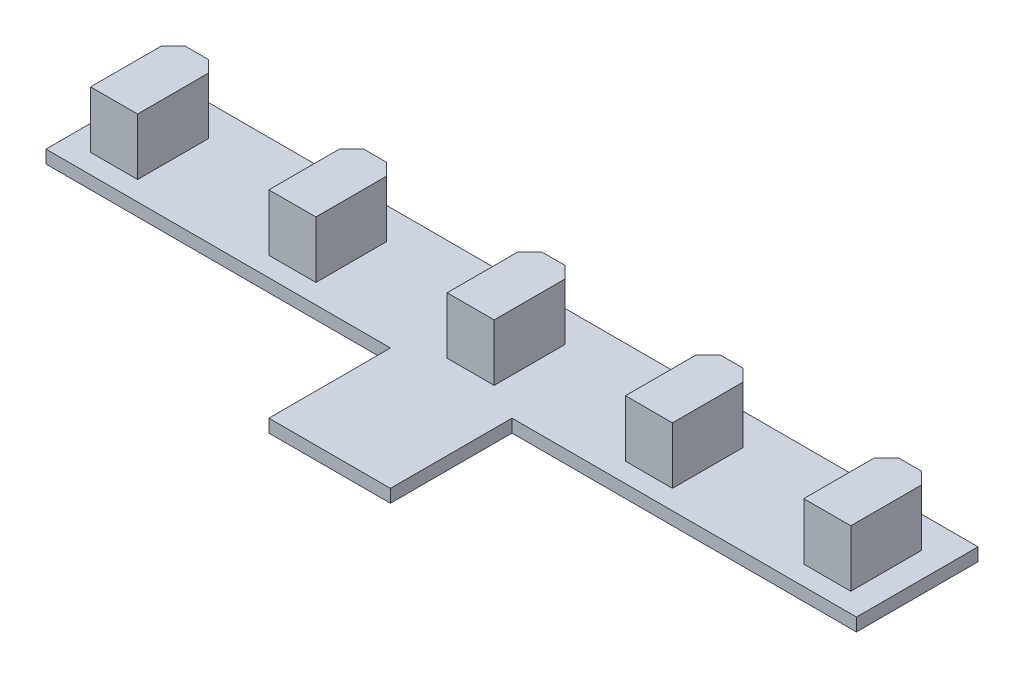
SolidWorks part; units mm, degrees
ref_plane "Front Plane" through (0, 0, 0) normal (0, 0, 1) x (1, 0, 0)
ref_plane "Top Plane" through (0, 0, 0) normal (0, 1, 0) x (1, 0, 0)
ref_plane "Right Plane" through (0, 0, 0) normal (1, 0, 0) x (0, 0, -1)
sketch "Sketch1" plane through (0, 0, 0) normal (0, 1, 0) x (1, 0, 0)
  line L0 (0, -55) -> (0, 55) construction
  line L1 (-7.5, -4.5) -> (7.5, -4.5)
  line L2 (-7.5, -4.5) -> (-7.5, 10.5)
  line L3 (-7.5, 10.5) -> (7.5, 10.5)
  line L4 (7.5, -4.5) -> (7.5, 10.5)
  line L5 (-7.5, -4.5) -> (7.5, 10.5) construction
  line L6 (-7.5, 10.5) -> (7.5, -4.5) construction
  line L7 (-5.28, -2.5) -> (5.28, -2.5)
  line L8 (-5.28, -2.5) -> (-5.28, 2.5)
  line L9 (-5.28, 2.5) -> (5.28, 2.5)
  line L10 (5.28, -2.5) -> (5.28, 2.5)
  line L11 (-5.28, -2.5) -> (5.28, 2.5) construction
  line L12 (-5.28, 2.5) -> (5.28, -2.5) construction
  line L13 (-2.9, 12.9) -> (2.9, 12.9)
  line L14 (-50, 25.5) -> (50, 25.5)
  line L15 (-50, 25.5) -> (-50, 10.5)
  line L16 (-50, 10.5) -> (50, 10.5)
  line L17 (50, 25.5) -> (50, 10.5)
  line L18 (-50, 25.5) -> (50, 10.5) construction
  line L19 (-50, 10.5) -> (50, 25.5) construction
  line L24 (-1.4307, 23.1) -> (1.4307, 23.1)
  line L25 (0, 12.9) -> (0, 23.1) construction
  line L26 (-2.9, 12.9) -> (-2.9, 21.6307)
  line L27 (-2.9, 21.6307) -> (-1.4307, 23.1)
  line L28 (1.4307, 23.1) -> (2.9, 21.6307)
  line L29 (2.9, 21.6307) -> (2.9, 12.9)
  line L30 (24.9, 21.6307) -> (24.9, 12.9)
  line L31 (19.1, 12.9) -> (24.9, 12.9)
  line L32 (19.1, 12.9) -> (19.1, 21.6307)
  line L33 (19.1, 21.6307) -> (20.5693, 23.1)
  line L34 (20.5693, 23.1) -> (23.4307, 23.1)
  line L35 (23.4307, 23.1) -> (24.9, 21.6307)
  line L36 (46.9, 21.6307) -> (46.9, 12.9)
  line L37 (41.1, 12.9) -> (46.9, 12.9)
  line L38 (41.1, 12.9) -> (41.1, 21.6307)
  line L39 (41.1, 21.6307) -> (42.5693, 23.1)
  line L40 (42.5693, 23.1) -> (45.4307, 23.1)
  line L41 (45.4307, 23.1) -> (46.9, 21.6307)
  line L42 (-19.1, 21.6307) -> (-19.1, 12.9)
  line L43 (-24.9, 12.9) -> (-19.1, 12.9)
  line L44 (-24.9, 12.9) -> (-24.9, 21.6307)
  line L45 (-24.9, 21.6307) -> (-23.4307, 23.1)
  line L46 (-23.4307, 23.1) -> (-20.5693, 23.1)
  line L47 (-20.5693, 23.1) -> (-19.1, 21.6307)
  line L48 (-41.1, 21.6307) -> (-41.1, 12.9)
  line L49 (-46.9, 12.9) -> (-41.1, 12.9)
  line L50 (-46.9, 12.9) -> (-46.9, 21.6307)
  line L51 (-46.9, 21.6307) -> (-45.4307, 23.1)
  line L52 (-45.4307, 23.1) -> (-42.5693, 23.1)
  line L53 (-42.5693, 23.1) -> (-41.1, 21.6307)
  point P0 (0, 3)
  point P5 (0, 0)
  point P13 (0, 18)
  point P15 (0, 18)
  point P26 (0, 18)
  dimension "D1" = 15
  dimension "D2" = 15
  dimension "D3" = 10.56
  dimension "D4" = 5
  dimension "D5" = 2
  dimension "D6" = 15
  dimension "D7" = 100
  dimension "D8" = 45
  dimension "D9" = 10.2
  dimension "D10" = 5.8
  dimension "D11" = 3
  dimension "D12" = 3
extrude "Boss-Extrude1" add sketch "Sketch1" along normal blind 1.6 contours L1 L4 L3 L2 L10 L7 L8 L9 | L7 L10 L9 L8 | L17 L14 L15 L16 L3 L28 L29 L13 L26 L27 L24 L34 L35 L30 L31 L32 L33 L40 L41 L36 L37 L38 L39 L46 L47 L42 L43 L44 L45 L52 L53 L48 L49 L50 L51 region at (0, 0, -3.9199) region at (-28.75, 0, -11.5112) region at (0, 0, 0)
extrude "Boss-Extrude2" add sketch "Sketch1<3>" against normal blind 2 contours L7 L10 L9 L8 region at (0, 0, 0)
sketch "Sketch1<3>" plane through (0, 0, 0) normal (0, 1, 0) x (1, 0, 0) same geometry as "Sketch1"
extrude "Boss-Extrude3" add sketch "Sketch1<4>" along normal blind 8.6 contours L35 L34 L33 L32 L31 L30 | L41 L40 L39 L38 L37 L36 | L29 L28 L24 L27 L26 L13 | L47 L46 L45 L44 L43 L42 | L53 L52 L51 L50 L49 L48 region at (0, 0, -17.8254) region at (22, 0, -17.8254) region at (44, 0, -17.8254) region at (-22, 0, -17.8254) region at (-44, 0, -17.8254)
sketch "Sketch1<4>" plane through (0, 0, 0) normal (0, 1, 0) x (1, 0, 0) same geometry as "Sketch1"
